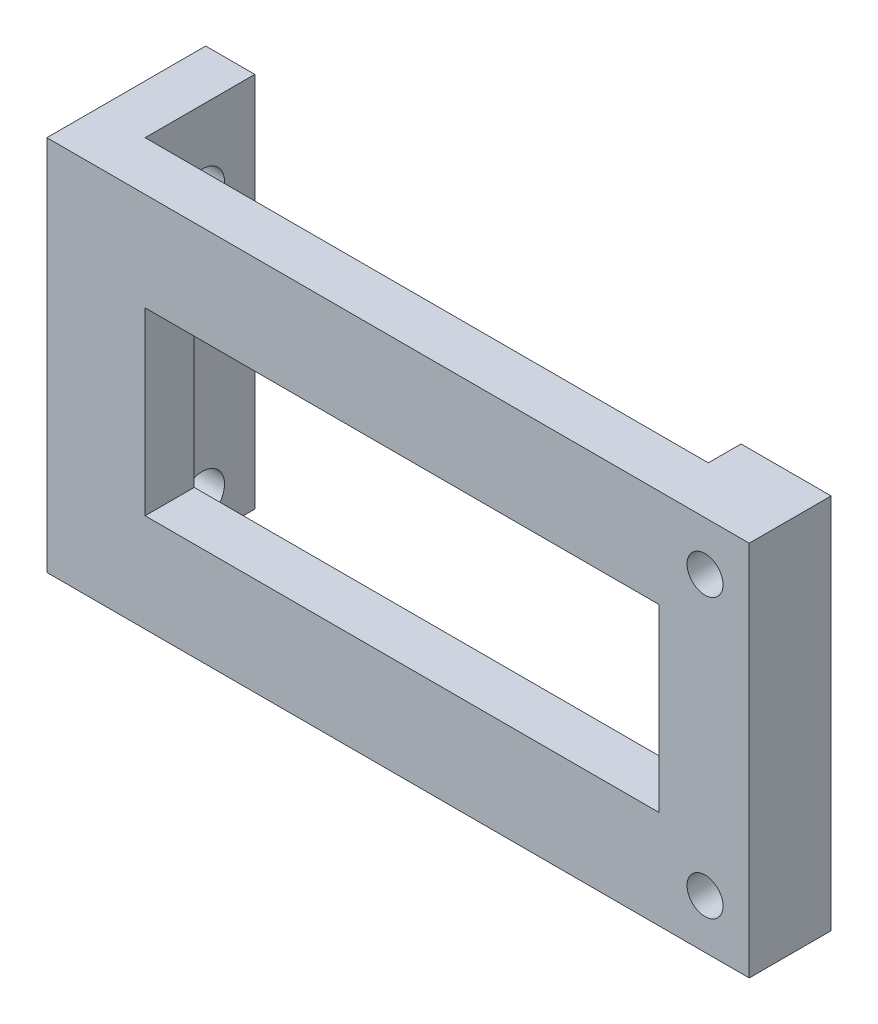
SolidWorks part; units mm, degrees
ref_plane "Front Plane" through (0, 0, 0) normal (0, 0, 1) x (1, 0, 0)
ref_plane "Top Plane" through (0, 0, 0) normal (0, 1, 0) x (1, 0, 0)
ref_plane "Right Plane" through (0, 0, 0) normal (1, 0, 0) x (0, 0, -1)
sketch "Sketch1" plane through (0, 0, 0) normal (0, 0, 1) x (1, 0, 0)
  line L0 (-15.45, 11.5) -> (-15.45, 5.5) construction
  line L1 (21.45, 11.5) -> (-21.45, 11.5)
  line L2 (21.45, 11.5) -> (21.45, -11.5)
  line L3 (21.45, -11.5) -> (-21.45, -11.5)
  line L4 (-21.45, 11.5) -> (-21.45, -11.5)
  line L5 (21.45, 11.5) -> (-21.45, -11.5) construction
  line L6 (21.45, -11.5) -> (-21.45, 11.5) construction
  line L7 (-21.45, 11.5) -> (-18.45, 11.5)
  line L8 (-21.45, 11.5) -> (-21.45, -11.5)
  line L9 (-21.45, -11.5) -> (-18.45, -11.5)
  line L10 (-18.45, 11.5) -> (-18.45, -11.5)
  line L11 (21.45, 11.5) -> (15.95, 11.5)
  line L12 (21.45, 11.5) -> (21.45, -11.5)
  line L13 (21.45, -11.5) -> (15.95, -11.5)
  line L14 (15.95, 11.5) -> (15.95, -11.5)
  line L15 (-15.45, 5.5) -> (15.95, 5.5)
  line L16 (-15.45, 5.5) -> (-15.45, -5.5)
  line L17 (-15.45, -5.5) -> (15.95, -5.5)
  line L18 (15.95, 5.5) -> (15.95, -5.5)
  line L19 (-15.45, 5.5) -> (-21.45, 5.5) construction
  line L20 (-15.45, -5.5) -> (-15.45, -11.5) construction
  circle A0 centre (18.75, -8.5) radius 1.1
  circle A1 centre (18.75, 8.5) radius 1.1
  point P0 (0, 0)
  dimension "D1" = 2.2
  dimension "D2" = 3
  dimension "D3" = 17
  dimension "D4" = 3
  dimension "D5" = 5.5
  dimension "D6" = 2.8
  dimension "D7" = 40.2
  dimension "D8" = 3
  dimension "D9" = 6
extrude "Boss-Extrude1" add sketch "Sketch1" against normal blind 3 contours L14 L1 L10 L3 region at (15.5362, 8.5, 0)
extrude "Boss-Extrude2" add sketch "Sketch1<3>" against normal blind 5 contours L1 L14 L3 L2 A1 A0 region at (18.6968, 0, 0)
sketch "Sketch1<3>" plane through (0, 0, 0) normal (0, 0, 1) x (1, 0, 0) same geometry as "Sketch1"
extrude "Boss-Extrude3" add sketch "Sketch1<4>" against normal blind 9.7 contours L10 L1 L4 L3 region at (-19.95, 0, 0)
sketch "Sketch1<4>" plane through (0, 0, 0) normal (0, 0, 1) x (1, 0, 0) same geometry as "Sketch1"
sketch "Sketch2" plane through (-21.45, 0, 0) normal (-1, 0, 0) x (0, 0, 1)
  line L1 (0, 11.5) -> (0, -11.5) construction
  circle A0 centre (-6.5, 6.75) radius 1.35
  dimension "D1" = 2.7
  dimension "D2" = 1.75
  dimension "D3" = 6.5
extrude "Cut-Extrude1" cut sketch "Sketch2" against normal up to surface (3 mm away) up to face at (-18.45, 0, -6.35)
pattern_linear "LPattern1" count 2 spacing 16 along (0, -1, 0) of "Cut-Extrude1"
move or copy body "Corpo-Mover/Copiar1" [suppressed] bodies to move or copy 105
move or copy body "Body-Move/Copy1" [suppressed] bodies to move or copy 105
